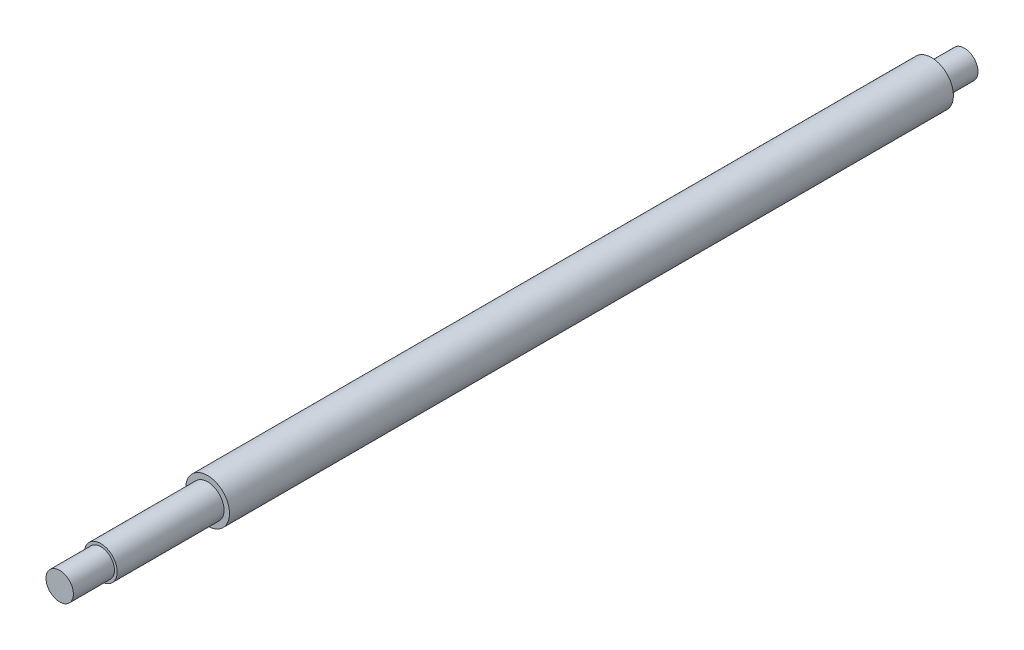
SolidWorks part; units mm, degrees
material "1060 Alloy"
ref_plane "Front Plane" through (0, 0, 0) normal (0, 0, 1) x (1, 0, 0)
ref_plane "Top Plane" through (0, 0, 0) normal (0, 1, 0) x (1, 0, 0)
ref_plane "Right Plane" through (0, 0, 0) normal (1, 0, 0) x (0, 0, -1)
sketch "Sketch1" plane through (0, 0, 0) normal (1, 0, 0) x (0, 0, -1)
  line L0 (0, 0) -> (-42.623, 0) construction
  line L1 (-318.98, 0) -> (-318.98, 5)
  line L2 (-318.98, 5) -> (-303.98, 5)
  line L3 (-303.98, 5) -> (-303.98, 6)
  line L4 (-303.98, 6) -> (-264.98, 6)
  line L5 (-264.98, 6) -> (-264.98, 8)
  line L6 (-264.98, 8) -> (-0.68, 8)
  line L7 (-0.68, 8) -> (-0.68, 5)
  line L8 (-0.68, 5) -> (11.32, 5)
  line L9 (11.32, 5) -> (11.32, 0)
  line L10 (-318.98, 0) -> (11.32, 0)
  line L12 (-6.68, 0) -> (-6.68, -14) construction
  point P2 (-139.727, -14)
  point P4 (0, 0)
  point P6 (0, 0)
  point P15 (0, 0)
  point P16 (-6.68, 0)
  point P20 (0, 0)
  point P22 (-152.3345, -14)
  dimension "D1" = 5
  dimension "D2" = 6
  dimension "D3" = 8
  dimension "D4" = 5
  dimension "D5" = 12
  dimension "D6" = 39
  dimension "D7" = 15
  dimension "D8" = 18
  dimension "D9" = 133.7816
revolve "Revolve1" add sketch "Sketch1" angle 360 about L0
sketch "Sketch3" [suppressed] plane through (0, 0, 0) normal (1, 0, 0) x (0, 0, -1)
  line L0 (-80.9254, 0) -> (-123.5483, 0) construction
  line L1 (-275.75, 0) -> (-275.75, 5)
  line L2 (-275.75, 5) -> (-260.75, 5)
  line L3 (-260.75, 5) -> (-260.75, 6)
  line L4 (-260.75, 6) -> (-221.75, 6)
  line L5 (-221.75, 6) -> (-221.75, 8)
  line L6 (-221.75, 8) -> (-12, 8)
  line L7 (-12, 8) -> (-12, 5)
  line L8 (-12, 5) -> (0, 5)
  line L9 (0, 5) -> (0, 0)
  line L10 (-275.75, 0) -> (0, 0)
  dimension "D1" = 10
  dimension "D2" = 6
  dimension "D3" = 8
  dimension "D4" = 10
  dimension "D5" = 15
  dimension "D6" = 39
  dimension "D7" = 209.75
  dimension "D8" = 12
revolve "Revolve2" [suppressed] add sketch "Sketch3" angle 360 about L0
